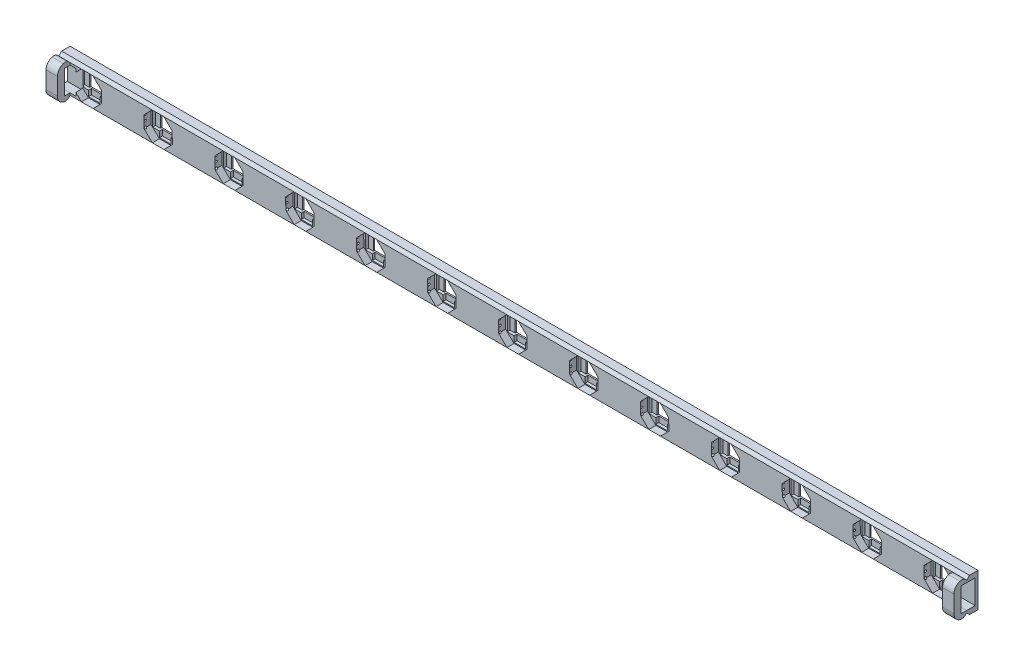
SolidWorks part; units mm, degrees
ref_plane "Front Plane" through (0, 0, 0) normal (0, 0, 1) x (1, 0, 0)
ref_plane "Top Plane" through (0, 0, 0) normal (0, 1, 0) x (1, 0, 0)
ref_plane "Right Plane" through (0, 0, 0) normal (1, 0, 0) x (0, 0, -1)
sketch "Sketch1" plane through (0, 0, 0) normal (0, 0, 1) x (1, 0, 0)
  line L1 (-329.6992, 7.2632) -> (-9.6992, 7.2632)
  line L2 (-329.6992, 7.2632) -> (-329.6992, -4.7368)
  line L3 (-329.6992, -4.7368) -> (-9.6992, -4.7368)
  line L4 (-9.6992, 7.2632) -> (-9.6992, -4.7368)
  dimension "D1" = 320
  dimension "D2" = 12
extrude "Boss-Extrude1" add sketch "Sketch1" along normal blind 4
sketch "Sketch3" plane through (0, 0, 4) normal (0, 0, 1) x (1, 0, 0)
  line L0 (-9.6992, -4.7368) -> (-9.6992, 7.2632) construction
  line L1 (-17.5892, -3.7205) -> (-14.6832, -0.7688)
  line L2 (-14.6832, -0.7688) -> (-14.7156, 3.3732)
  line L3 (-14.7156, 3.3732) -> (-17.6673, 6.2792)
  line L4 (-17.6673, 6.2792) -> (-21.8093, 6.2468)
  line L5 (-21.8093, 6.2468) -> (-24.7153, 3.2951)
  line L6 (-24.7153, 3.2951) -> (-24.6829, -0.8469)
  line L7 (-24.6829, -0.8469) -> (-21.7312, -3.7529)
  line L8 (-21.7312, -3.7529) -> (-17.5892, -3.7205)
  line L9 (-329.6992, -4.7368) -> (-9.6992, -4.7368) construction
  circle A0 centre (-19.6992, 1.2632) radius 5 construction
  dimension "D3" = 10
  dimension "D1" = 10
  dimension "D2" = 6
extrude "Cut-Extrude1" cut sketch "Sketch3" against normal blind 2.5
sketch "Sketch4" plane through (0, 0, 1.5) normal (0, 0, 1) x (1, 0, 0)
  line L1 (-22.3492, 3.9132) -> (-17.0492, 3.9132)
  line L2 (-22.3492, 3.9132) -> (-22.3492, -1.3868)
  line L3 (-22.3492, -1.3868) -> (-17.0492, -1.3868)
  line L4 (-17.0492, 3.9132) -> (-17.0492, -1.3868)
  line L13 (-9.6992, -4.7368) -> (-9.6992, 7.2632) construction
  line L14 (-329.6992, -4.7368) -> (-9.6992, -4.7368) construction
  dimension "D1" = 5.3
  dimension "D2" = 5.3
  dimension "D3" = 7.35
  dimension "D4" = 3.35
extrude "Cut-Extrude2" cut sketch "Sketch4" against normal through all
sketch "Sketch6" plane through (0, 0, 1.5) normal (0, 0, 1) x (1, 0, 0)
  line L0 (-22.3492, -1.3868) -> (-17.0492, -1.3868) construction
  line L1 (-21.6992, -1.3868) -> (-17.6992, -1.3868)
  line L2 (-21.6992, -1.3868) -> (-21.6992, -3.3868)
  line L3 (-21.6992, -3.3868) -> (-17.6992, -3.3868)
  line L4 (-17.6992, -1.3868) -> (-17.6992, -3.3868)
  line L7 (-9.6992, -4.7368) -> (-9.6992, 7.2632) construction
  line L8 (-329.6992, -4.7368) -> (-9.6992, -4.7368) construction
  dimension "D1" = 4
  dimension "D2" = 2
  dimension "D3" = 8
  dimension "D4" = 1.35
extrude "Cut-Extrude3" cut sketch "Sketch6" against normal blind 1
sketch "Sketch7" plane through (0, 0, 1.5) normal (0, 0, 1) x (1, 0, 0)
  line L0 (-17.0492, 3.9132) -> (-22.3492, 3.9132) construction
  line L1 (-21.6992, 3.9132) -> (-17.6992, 3.9132)
  line L2 (-21.6992, 3.9132) -> (-21.6992, 5.9132)
  line L3 (-21.6992, 5.9132) -> (-17.6992, 5.9132)
  line L4 (-17.6992, 3.9132) -> (-17.6992, 5.9132)
  line L6 (-9.6992, -4.7368) -> (-9.6992, 7.2632) construction
  dimension "D1" = 2
  dimension "D2" = 4
  dimension "D3" = 8
extrude "Cut-Extrude4" cut sketch "Sketch7" against normal blind 1
sketch "Sketch10" plane through (0, 0, 1.5) normal (0, 0, 1) x (1, 0, 0)
  line L1 (-17.0492, 3.9132) -> (-15.2992, 3.9132)
  line L2 (-17.0492, 3.9132) -> (-17.0492, -1.4203)
  line L3 (-17.0492, -1.4203) -> (-15.2992, -1.4203)
  line L4 (-15.2992, 3.9132) -> (-15.2992, -1.4203)
  line L5 (-22.3492, -1.3868) -> (-24.0992, -1.3868)
  line L6 (-22.3492, -1.3868) -> (-22.3492, 3.9132)
  line L7 (-22.3492, 3.9132) -> (-24.0992, 3.9132)
  line L8 (-24.0992, -1.3868) -> (-24.0992, 3.9132)
  dimension "D1" = 1.75
  dimension "D2" = 1.75
extrude "Cut-Extrude7" cut sketch "Sketch10" against normal blind 1
sketch "Sketch11" plane through (-9.6992, 0, 0) normal (1, 0, 0) x (0, 0, -1)
  line L0 (-4, -4.7368) -> (0, -4.7368) construction
  line L1 (-4, -4.7368) -> (-4, 7.2632) construction
  circle A0 centre (-3.5, 1.2632) radius 0.375
  dimension "D2" = 0.75
  dimension "D1" = 6
  dimension "D3" = 0.5
extrude "Cut-Extrude8" cut sketch "Sketch11" against normal through all both and the other way through all
sketch "Sketch12" plane through (-9.6992, 0, 0) normal (1, 0, 0) x (0, 0, -1)
  line L0 (-4, -4.7368) -> (-4, 7.2632) construction
  circle A0 centre (-3.5, -0.7368) radius 0.375
  circle A1 centre (-3.5, 1.2632) radius 0.375 construction
  dimension "D3" = 0.75
  dimension "D1" = 2
  dimension "D2" = 0.5
extrude "Cut-Extrude9" cut sketch "Sketch12" against normal through all both and the other way through all
sketch "Sketch13" plane through (-9.6992, 0, 0) normal (1, 0, 0) x (0, 0, -1)
  line L0 (-4, -4.7368) -> (-4, 7.2632) construction
  circle A0 centre (-3.5, 3.2632) radius 0.375
  circle A1 centre (-3.5, 1.2632) radius 0.375 construction
  dimension "D3" = 0.75
  dimension "D1" = 2
  dimension "D2" = 0.5
extrude "Cut-Extrude10" cut sketch "Sketch13" against normal through all both and the other way through all
sketch "Sketch14" plane through (0, 0, 4) normal (0, 0, 1) x (1, 0, 0)
  line L0 (-9.6992, -4.7368) -> (-9.6992, 7.2632) construction
  line L1 (-15.6992, 5.5132) -> (-9.6992, 5.5132)
  line L2 (-15.6992, 5.5132) -> (-15.6992, -2.9868)
  line L3 (-15.6992, -2.9868) -> (-9.6992, -2.9868)
  line L4 (-9.6992, 5.5132) -> (-9.6992, -2.9868)
  line L5 (-329.6992, -4.7368) -> (-9.6992, -4.7368) construction
  dimension "D1" = 8.5
  dimension "D2" = 1.75
  dimension "D3" = 6
extrude "Cut-Extrude11" cut sketch "Sketch14" against normal blind 3 and the other way through all
sketch "Sketch15" plane through (0, 0, 4) normal (0, 0, 1) x (1, 0, 0)
  line L0 (-329.6992, -4.7368) -> (-9.6992, -4.7368) construction
  line L1 (-9.6992, 7.2632) -> (-13.6992, 7.2632)
  line L2 (-9.6992, 7.2632) -> (-9.6992, -4.7368)
  line L3 (-9.6992, -4.7368) -> (-13.6992, -4.7368)
  line L4 (-13.6992, 7.2632) -> (-13.6992, -4.7368)
  dimension "D1" = 4
extrude "Boss-Extrude2" add sketch "Sketch15" along normal blind 4.5
sketch "Sketch16" plane through (-9.6992, 0, 0) normal (1, 0, 0) x (0, 0, -1)
  line L1 (-4, 5.5132) -> (-6, 5.5132)
  line L2 (-4, 5.5132) -> (-4, -2.9871)
  line L3 (-4, -2.9871) -> (-6, -2.9871)
  line L4 (-6, 5.5132) -> (-6, -2.9871)
  dimension "D1" = 2
extrude "Cut-Extrude12" cut sketch "Sketch16" against normal blind 4.5
fillet "Fillet1" radius 3 1 edges at (-11.6992, 7.2632, 8.5)
fillet "Fillet2" radius 3 1 edges at (-11.6992, -4.7368, 8.5)
sketch "Sketch17" plane through (0, 0, 4) normal (0, 0, 1) x (1, 0, 0)
  line L0 (-329.6992, 7.2632) -> (-329.6992, -4.7368) construction
  line L1 (-329.6992, 5.5132) -> (-323.6992, 5.5132)
  line L2 (-329.6992, 5.5132) -> (-329.6992, -2.9868)
  line L3 (-329.6992, -2.9868) -> (-323.6992, -2.9868)
  line L4 (-323.6992, 5.5132) -> (-323.6992, -2.9868)
  line L5 (-329.6992, -4.7368) -> (-13.6992, -4.7368) construction
  dimension "D1" = 6
  dimension "D2" = 8.5
  dimension "D3" = 1.75
extrude "Cut-Extrude13" cut sketch "Sketch17" against normal blind 3
sketch "Sketch18" plane through (0, 0, 4) normal (0, 0, 1) x (1, 0, 0)
  line L0 (-329.6992, -4.7368) -> (-13.6992, -4.7368) construction
  line L1 (-329.6992, 7.2632) -> (-325.6992, 7.2632)
  line L2 (-329.6992, 7.2632) -> (-329.6992, -4.7368)
  line L3 (-329.6992, -4.7368) -> (-325.6992, -4.7368)
  line L4 (-325.6992, 7.2632) -> (-325.6992, -4.7368)
  dimension "D1" = 4
extrude "Boss-Extrude3" add sketch "Sketch18" along normal blind 4.5
sketch "Sketch19" plane through (-329.6992, 0, 0) normal (-1, 0, 0) x (0, 0, 1)
  line L1 (4, 5.5132) -> (6, 5.5132)
  line L2 (4, 5.5132) -> (4, -2.9862)
  line L3 (4, -2.9862) -> (6, -2.9862)
  line L4 (6, 5.5132) -> (6, -2.9862)
  dimension "D1" = 2
extrude "Cut-Extrude14" cut sketch "Sketch19" against normal blind 4.5
fillet "Fillet3" radius 3 1 edges at (-327.6992, 7.2632, 8.5)
fillet "Fillet4" radius 3 1 edges at (-327.6992, -4.7368, 8.5)
chamfer "Chamfer1" distance 1 angle 45 1 edges at (-169.6992, 7.2632, 4)
chamfer "Chamfer2" distance 1 angle 45 1 edges at (-169.6992, -4.7368, 4)
sketch "Sketch30" plane through (-325.6992, 0, 0) normal (1, 0, 0) x (0, 0, -1)
  line L0 (-3, -4.7368) -> (-4, -3.7368)
  line L1 (-4, -3.7368) -> (-4, -4.7368)
  line L2 (-5.5, -4.7368) -> (-3, -4.7368) construction
  line L3 (-4, -4.7368) -> (-3, -4.7368)
extrude "Cut-Extrude15" cut sketch "Sketch30" along normal through all both and the other way through all
sketch "Sketch31" plane through (-325.6992, 0, 0) normal (1, 0, 0) x (0, 0, -1)
  line L0 (-4, 6.2632) -> (-3, 7.2632)
  line L1 (-3, 7.2632) -> (-4, 7.2632)
  line L2 (-5.5, 7.2632) -> (-3, 7.2632) construction
  line L3 (-4, 7.2632) -> (-4, 6.2632)
extrude "Cut-Extrude16" cut sketch "Sketch31" against normal through all both and the other way through all
chamfer "Chamfer3" distance 1 angle 45 1 edges at (-327.6992, 7.2632, 4)
chamfer "Chamfer4" distance 1 angle 45 1 edges at (-11.6992, 7.2632, 4)
chamfer "Chamfer5" distance 1 angle 45 1 edges at (-11.6992, -4.7368, 4)
chamfer "Chamfer6" distance 1 angle 45 1 edges at (-327.6992, -4.7368, 4)
fillet "Fillet5" radius 2 1 edges at (-11.6992, 7.2632, 5)
fillet "Fillet6" radius 2 1 edges at (-11.6992, -4.7368, 5)
fillet "Fillet7" radius 2 1 edges at (-327.6992, -4.7368, 5)
fillet "Fillet8" radius 2 1 edges at (-327.6992, 7.2632, 5)
pattern_linear "LPattern1" count 13 spacing 25 along (-1, 0, 0) of "Cut-Extrude1", "Cut-Extrude2", "Cut-Extrude3", "Cut-Extrude4", "Cut-Extrude7"
